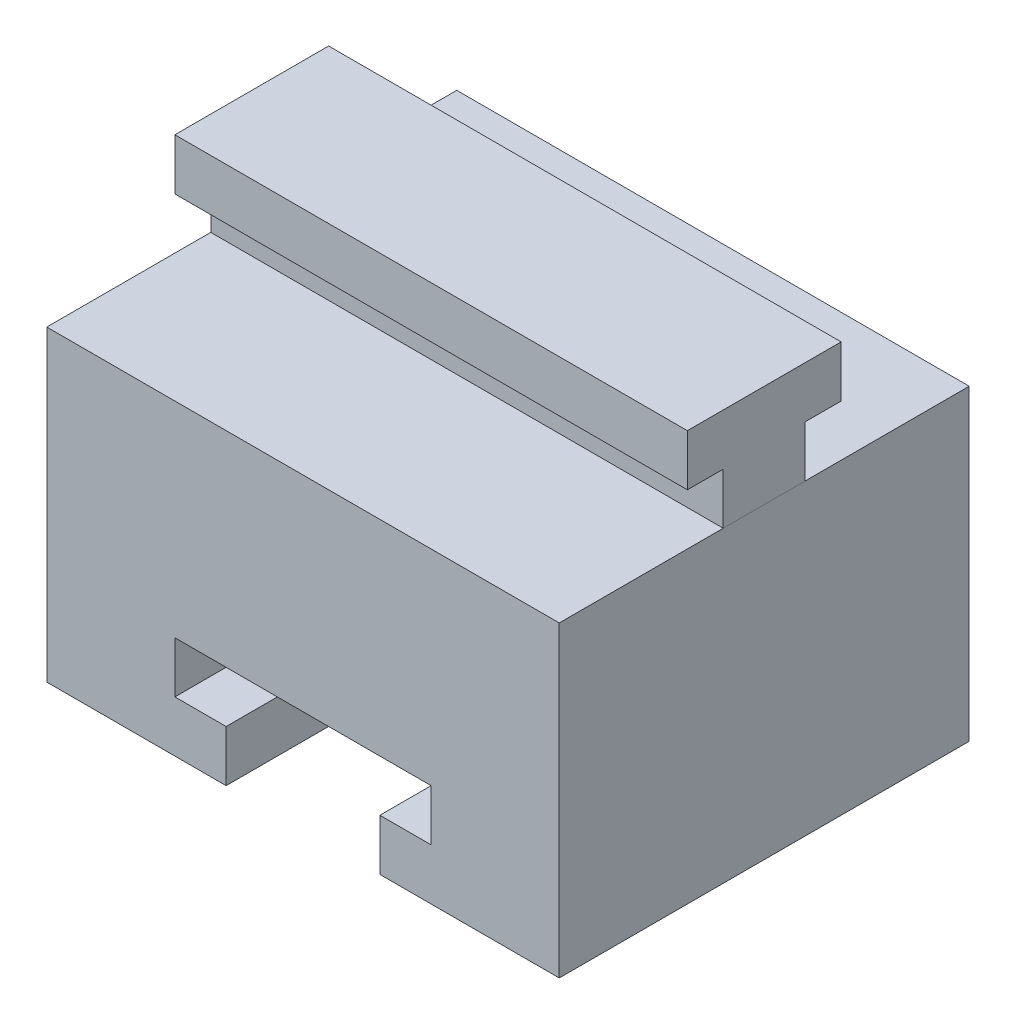
SolidWorks part; units mm, degrees
other "DetailItem3"
other "DetailItem4"
other "Weld Folder"
other "Weld Bead3"
other "Weld Bead4"
ref_plane "Front Plane" through (0, 0, 0) normal (0, 0, 1) x (1, 0, 0)
ref_plane "Top Plane" through (0, 0, 0) normal (0, 1, 0) x (1, 0, 0)
ref_plane "Right Plane" through (0, 0, 0) normal (1, 0, 0) x (0, 0, -1)
sketch "Sketch1" plane through (0, 0, 0) normal (0, 0, 1) x (1, 0, 0)
  line L1 (-37.7143, 8.1429) -> (12.2857, 8.1429)
  line L2 (-37.7143, 8.1429) -> (-37.7143, -21.8571)
  line L3 (-37.7143, -21.8571) -> (12.2857, -21.8571)
  line L4 (12.2857, 8.1429) -> (12.2857, -21.8571)
  dimension "D1" = 30
  dimension "D2" = 50
extrude "Boss-Extrude1" add sketch "Sketch1" along normal blind 40
sketch "Sketch2" plane through (0, 0, 40) normal (0, 0, 1) x (1, 0, 0)
  line L0 (-37.7143, -21.8571) -> (-25.2143, -21.8571) construction
  line L1 (-37.7143, -21.8571) -> (12.2857, -21.8571) construction
  line L2 (12.2857, -21.8571) -> (-0.2143, -21.8571) construction
  line L4 (-20.2143, -21.8571) -> (-20.2143, -16.8571)
  line L5 (-20.2143, -16.8571) -> (-25.2143, -16.8571)
  line L6 (-25.2143, -16.8571) -> (-25.2143, -11.8571)
  line L7 (-25.2143, -11.8571) -> (-0.2143, -11.8571)
  line L8 (-0.2143, -11.8571) -> (-0.2143, -16.8571)
  line L9 (-0.2143, -16.8571) -> (-5.2143, -16.8571)
  line L10 (-5.2143, -16.8571) -> (-5.2143, -21.8571)
  dimension "D2" = 12.5
  dimension "D3" = 5
extrude "Cut-Extrude12" cut sketch "Sketch2" against normal through all both and the other way through all flip side to cut
sketch "Sketch3" plane through (0, 0, 0) normal (1, 0, 0) x (0, 0, -1)
  line L0 (-24, 8.1429) -> (-16, 8.1429)
  line L1 (-40, 8.1429) -> (0, 8.1429) construction
  line L3 (-24, 8.1429) -> (-24, 13.1395)
  line L4 (-24, 13.1395) -> (-27.5, 13.1395)
  line L5 (-27.5, 13.1395) -> (-27.5, 18.1395)
  line L6 (-16, 8.1429) -> (-16, 13.1395)
  line L7 (-16, 13.1395) -> (-12.5, 13.1395)
  line L8 (-12.5, 13.1395) -> (-12.5, 18.1395)
  line L9 (-12.5, 18.1395) -> (-27.5, 18.1395)
  dimension "D3" = 3.5
  dimension "D4" = 5
  dimension "D5" = 3.5
extrude "Boss-Extrude2" add sketch "Sketch3" along normal through all and the other way through all separate body
